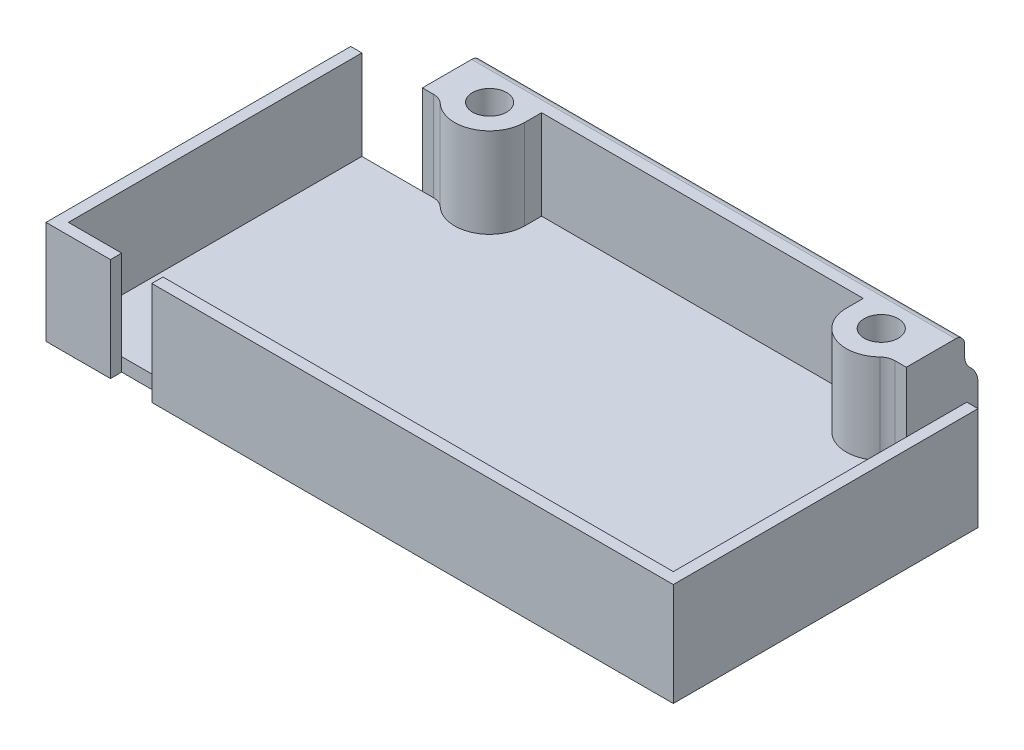
SolidWorks part; units mm, degrees
note: The reader was unsure of these and kept them because the rebuilt part matched: shared geometry of "Sketch6<3>".
ref_plane "Front Plane" through (0, 0, 0) normal (0, 0, 1) x (1, 0, 0)
ref_plane "Top Plane" through (0, 0, 0) normal (0, 1, 0) x (1, 0, 0)
ref_plane "Right Plane" through (0, 0, 0) normal (1, 0, 0) x (0, 0, -1)
sketch "Sketch1" plane through (0, 0, 0) normal (0, 1, 0) x (1, 0, 0)
  line L0 (35, 14.25) -> (27, 14.25)
  line L1 (-35, -19.75) -> (35, -19.75)
  line L2 (-35, -19.75) -> (-35, 14.25)
  line L3 (-27, 19.75) -> (27, 19.75)
  line L4 (35, -19.75) -> (35, 14.25)
  line L5 (-35, -19.75) -> (35, 19.75) construction
  line L6 (-35, 19.75) -> (35, -19.75) construction
  line L7 (27, 14.25) -> (27, 19.75)
  line L8 (0, -980.25) -> (0, 49019.75) construction
  line L9 (-27, 14.25) -> (-27, 19.75)
  line L10 (-35, 14.25) -> (-27, 14.25)
  line L11 (35, 14.25) -> (35, 19.75) construction
  line L12 (35, 19.75) -> (27, 19.75) construction
  line L13 (-27, 19.75) -> (-35, 19.75) construction
  line L14 (-35, 19.75) -> (-35, 14.25) construction
  point P0 (0, 0)
  dimension "D1" = 70
  dimension "D2" = 39.5
  dimension "D3" = 8
  dimension "D4" = 5.5
extrude "Boss-Extrude1" add sketch "Sketch1" along normal blind 11.5
sketch "Sketch2" plane through (0, 11.5, 0) normal (0, 1, 0) x (1, 0, 0)
  line L30 (-33.75, 13) -> (-33.75, -18.5)
  line L31 (-33.75, -18.5) -> (33.75, -18.5)
  line L32 (33.75, -18.5) -> (33.75, 13)
  line L33 (33.75, 13) -> (25.75, 13)
  line L34 (25.75, 13) -> (25.75, 18.5)
  line L35 (25.75, 18.5) -> (-25.75, 18.5)
  line L36 (-25.75, 18.5) -> (-25.75, 13)
  line L37 (-25.75, 13) -> (-33.75, 13)
  line L38 (-33.75, 13) -> (-33.75, -18.5)
  line L39 (-33.75, -18.5) -> (33.75, -18.5)
  line L40 (33.75, -18.5) -> (33.75, 13)
  line L41 (33.75, 13) -> (25.75, 13)
  line L42 (25.75, 13) -> (25.75, 18.5)
  line L43 (25.75, 18.5) -> (-25.75, 18.5)
  line L44 (-25.75, 18.5) -> (-25.75, 13)
  line L45 (-25.75, 13) -> (-33.75, 13)
  dimension "D1" = 1.25
extrude "Cut-Extrude1" cut sketch "Sketch2" against normal offset from surface (10 mm away) 1.5 up to face at (0, 0, -7.125)
sketch "Sketch4" plane through (0, 0, -14.25) normal (0, 0, -1) x (-1, 0, 0)
  line L1 (-33.75, 11.5) -> (-27, 11.5)
  line L2 (-33.75, 11.5) -> (-33.75, 1.5)
  line L3 (-33.75, 1.5) -> (-27, 1.5)
  line L4 (-27, 11.5) -> (-27, 1.5)
  line L5 (-27, 11.5) -> (-27, 0) construction
  line L6 (-33.75, 1.5) -> (-25.75, 1.5) construction
  line L7 (-33.75, 1.5) -> (-33.75, 11.5) construction
  line L8 (-33.75, 11.5) -> (-25.75, 11.5) construction
extrude "Cut-Extrude3" cut sketch "Sketch4" against normal up to next
mirror "Mirror1" about plane through (0, 0, 0) normal (1, 0, 0) of "Cut-Extrude3"
sketch "Sketch5" plane through (27, 0, 0) normal (1, 0, 0) x (0, 0, -1)
  line L1 (13, 11.5) -> (14.25, 11.5)
  line L2 (13, 11.5) -> (13, 1.5)
  line L3 (13, 1.5) -> (14.25, 1.5)
  line L4 (14.25, 11.5) -> (14.25, 1.5)
extrude "Cut-Extrude4" cut sketch "Sketch5" against normal up to surface (54 mm away) up to face at (-27, 4.3333, -15.6667)
sketch "Sketch6" plane through (0, 11.5, 0) normal (0, 1, 0) x (1, 0, 0)
  line L0 (25.75, 16.6) -> (25.75, 19.7943) construction
  line L1 (17.95, 16.6) -> (17.95, 19.7943) construction
  line L2 (-17.95, 16.6) -> (-17.95, 19.7943) construction
  line L3 (-25.75, 16.6) -> (-25.75, 19.7943) construction
  line L4 (25.75, 16.6) -> (25.75, 19.7943)
  line L5 (17.95, 16.6) -> (17.95, 19.7943)
  line L6 (-17.95, 16.6) -> (-17.95, 19.7943)
  line L7 (-25.75, 16.6) -> (-25.75, 19.7943)
  line L8 (25.75, 19.75) -> (17.95, 19.75)
  line L9 (14, 19.75) -> (27, 19.75) construction
  line L10 (-17.95, 19.75) -> (-25.75, 19.75)
  line L11 (-27, 19.75) -> (-14, 19.75) construction
  line L12 (-27, 14.25) -> (-25.75, 14.25) construction
  line L13 (0, -6.3525) -> (0, 6.3525) construction
  circle A0 centre (21.85, 16.6) radius 1.9 construction
  arc A1 (17.95, 16.6) -> (25.75, 16.6) centre (21.85, 16.6) ccw construction
  arc A2 (-25.75, 16.6) -> (-17.95, 16.6) centre (-21.85, 16.6) ccw construction
  circle A3 centre (-21.85, 16.6) radius 1.9 construction
  circle A4 centre (21.85, 16.6) radius 1.9
  arc A5 (17.95, 16.6) -> (25.75, 16.6) centre (21.85, 16.6) ccw
  arc A6 (-25.75, 16.6) -> (-17.95, 16.6) centre (-21.85, 16.6) ccw
  circle A7 centre (-21.85, 16.6) radius 1.9
  circle A8 centre (-25.75, 12.4685) radius 1.7815
  circle A9 centre (25.75, 12.4685) radius 1.7815
  line M5 (-25.75, 14.25) -> (-25.75, 18.5)
  line M6 (-25.75, 18.5) -> (25.75, 18.5)
  line M7 (25.75, 18.5) -> (25.75, 14.25)
  line M10 (27, 19.75) -> (-27, 19.75)
extrude "Boss-Extrude2" add sketch "Sketch6" against normal up to next contours L5 A5 A4 M7 M6 | L5 L4 M6 M10 | A7 A6 L6 M6 M5 | L7 L6 M6 M10 | A8 A6 M5 | A5 A9 M7
extrude "Cut-Extrude5" cut sketch "Sketch6<3>" against normal through all both and the other way through all contours A7 | A4
sketch "Sketch6<3>" plane through (0, 11.5, 0) normal (0, 1, 0) x (1, 0, 0) same geometry as "Sketch6"
sketch "Sketch8" plane through (0, 0, 0) normal (0, -1, 0) x (1, 0, 0)
  line L0 (-27.8049, 19.75) -> (-27.8049, 18.5)
  line L1 (-33.75, 18.5) -> (33.75, 18.5) construction
  line L2 (-27.8049, 18.5) -> (-23.1951, 18.5)
  line L3 (-23.1951, 18.5) -> (-23.1951, 19.75)
  circle A0 centre (-25.5, 21.25) radius 2.75
  line M11 (35, 19.75) -> (-35, 19.75)
  dimension "D1" = 5.5
extrude "Cut-Extrude8" cut sketch "Sketch8" against normal through all contours A0 L0 L2 | A0 M11 | A0 L2 L3
sketch "Sketch9" plane through (27, 0, 0) normal (1, 0, 0) x (0, 0, -1)
  line L1 (22.25, 0) -> (19.75, 0)
  line L2 (19.75, 0) -> (19.75, 11.5)
  line L3 (22.25, 0) -> (22.25, 6)
  line L4 (20.75, 9.362) -> (20.75, 10.5)
  line L5 (14.25, 11.5) -> (19.75, 11.5) construction
  circle A0 centre (22.7678, 9.362) radius 2.0178
  circle A2 centre (19.75, 6) radius 2.5
  circle A3 centre (19.75, 10.5) radius 1
  point P16 (20.7011, 2.3245)
  point P17 (0, 0)
  point P18 (22.6068, 9.488)
  line M14 (19.75, 0) -> (19.75, 11.5)
  dimension "D2" = 6
  dimension "D3" = 2
  dimension "D1" = 2.5
extrude "Boss-Extrude3" add sketch "Sketch9" against normal up to surface (54 mm away) contours A3 L2 | A3 A2 A0 L4 M14 | A2 L2 | A2 L1 L3 M14 up to face at (-27, 4.9, -16.45)
sketch "Sketch10" plane through (0, 0, -22.25) normal (0, 0, -1) x (-1, 0, 0)
  line L0 (-23.75, 5.3636) -> (-19.95, 5.3636) construction
  line L1 (-23.75, 11.5) -> (-23.75, 0) construction
  line L2 (-19.95, 0) -> (-19.95, 11.5) construction
  line L5 (0, -1000) -> (0, 49000) construction
  line L12 (27, 5.5) -> (-27, 5.5)
  line L13 (27, 5.5) -> (-27, 5.5) construction
  line L15 (27, 0.5) -> (-27, 0.5)
  line L16 (27, 0.5) -> (-27, 0.5) construction
  circle A0 centre (-21.85, 3) radius 1.5
  circle A1 centre (-21.85, 3) radius 2.5
  circle A2 centre (21.85, 3) radius 1.5
  circle A3 centre (21.85, 3) radius 2.5
  point P10 (-21.85, 5.3636)
  dimension "D1" = 1
  dimension "D2" = 0.5
  dimension "D3" = 0.5
extrude "Boss-Extrude4" add sketch "Sketch10" along normal blind 2.5
fillet "Fillet1" radius 1.5 2 edges at (-21.85, 0.5, -22.25) (21.85, 5.5, -22.25)
fillet "Fillet2" radius 0.5 2 edges at (-21.85, 0.5, -24.75) (21.85, 5.5, -24.75)
